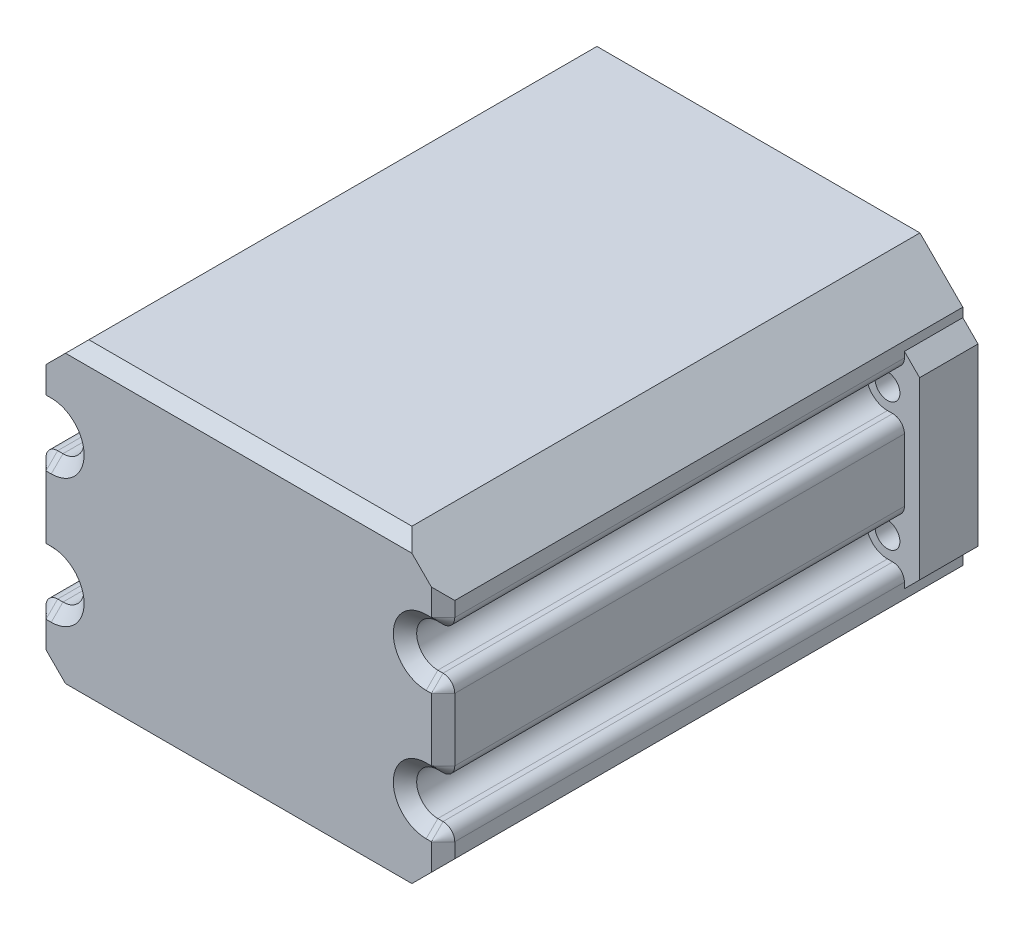
SolidWorks part; units mm, degrees
note: The reader was unsure of these and kept them because the rebuilt part matched: shared geometry of "Sketch1<3>".
ref_plane "Front Plane" through (0, 0, 0) normal (0, 0, 1) x (1, 0, 0)
ref_plane "Top Plane" through (0, 0, 0) normal (0, 1, 0) x (1, 0, 0)
ref_plane "Right Plane" through (0, 0, 0) normal (1, 0, 0) x (0, 0, -1)
sketch "Sketch1" plane through (0, 0, 0) normal (0, 0, 1) x (1, 0, 0)
  line L0 (27.6569, 53) -> (27.6569, 0) construction
  line L2 (-3.3431, 9.6017) -> (-3.3431, 9)
  line L4 (-4.4431, 41.125) -> (-7.3431, 41.125)
  line L5 (-4.4431, 33.875) -> (-7.3431, 33.875)
  line L6 (-4.4431, 11.875) -> (-7.3431, 11.875)
  line L7 (-4.4431, 19.125) -> (-7.3431, 19.125)
  line L8 (-7.3431, 41.5) -> (-9.9431, 41.5)
  line L13 (-9.9431, 41.5) -> (-9.9431, 11.5)
  line L17 (55.3137, 53) -> (0, 53)
  line L18 (0, 53) -> (-7.3431, 45.6569)
  line L19 (-7.3431, 45.6569) -> (-7.3431, 41.125)
  line L20 (-7.3431, 7.3431) -> (0, 0)
  line L21 (0, 0) -> (55.3137, 0)
  line L28 (-7.3431, 11.875) -> (-7.3431, 7.3431)
  line L29 (-7.3431, 33.875) -> (-7.3431, 19.125)
  line L30 (-7.3431, 33.875) -> (-7.3431, 19.125)
  line L33 (27.6569, 49) -> (1.6569, 49)
  line L37 (1.6569, 4) -> (27.6569, 4)
  line L38 (-3.3431, 9) -> (1.6569, 4)
  line L44 (1.5569, 37.5) -> (1.5569, 15.5)
  line L46 (1.6569, 49) -> (-3.3431, 44)
  line L47 (-3.3431, 44) -> (-3.3431, 43.3983)
  line L50 (-9.9431, 11.5) -> (-7.3431, 11.5)
  line L57 (65.2569, 11.5) -> (62.6569, 11.5)
  line L58 (58.6569, 44) -> (58.6569, 43.3983)
  line L59 (53.6569, 49) -> (58.6569, 44)
  line L60 (53.7569, 37.5) -> (53.7569, 15.5)
  line L61 (58.6569, 9) -> (53.6569, 4)
  line L62 (53.6569, 4) -> (27.6569, 4)
  line L63 (27.6569, 49) -> (53.6569, 49)
  line L64 (62.6569, 33.875) -> (62.6569, 19.125)
  line L66 (62.6569, 33.875) -> (62.6569, 19.125)
  line L67 (62.6569, 11.875) -> (62.6569, 7.3431)
  line L68 (62.6569, 7.3431) -> (55.3137, 0)
  line L70 (62.6569, 45.6569) -> (62.6569, 41.125)
  line L71 (55.3137, 53) -> (62.6569, 45.6569)
  line L72 (65.2569, 41.5) -> (65.2569, 11.5)
  line L73 (62.6569, 41.5) -> (65.2569, 41.5)
  line L74 (59.7569, 19.125) -> (62.6569, 19.125)
  line L75 (59.7569, 11.875) -> (62.6569, 11.875)
  line L76 (59.7569, 33.875) -> (62.6569, 33.875)
  line L77 (59.7569, 41.125) -> (62.6569, 41.125)
  line L78 (58.6569, 9.6017) -> (58.6569, 9)
  line L79 (-9.9431, 41.5) -> (-9.9431, 11.5) construction
  line L80 (-9.9431, 41.5) -> (-7.3431, 44.1)
  line L81 (-9.9431, 11.5) -> (-7.3431, 8.9)
  line L82 (-7.3431, 8.9) -> (-7.3431, 11.5)
  line L83 (-7.3431, 44.1) -> (-7.3431, 41.5)
  line L84 (62.6569, 41.5) -> (65.2569, 41.5)
  line L85 (65.2569, 41.5) -> (62.6569, 44.1)
  line L86 (65.2569, 41.5) -> (62.6569, 44.1) construction
  line L87 (62.6569, 44.1) -> (62.6569, 41.5)
  line L88 (65.2569, 11.5) -> (62.6569, 8.9)
  line L89 (62.6569, 8.9) -> (65.2569, 11.5) construction
  line L90 (62.6569, 8.9) -> (62.6569, 11.5)
  arc A0 (-4.4431, 33.875) -> (-4.4431, 41.125) centre (-4.4431, 37.5) ccw
  circle A1 centre (-4.4431, 15.5) radius 2.125
  circle A4 centre (-4.4431, 37.5) radius 2.125
  arc A5 (-4.4431, 11.875) -> (-4.4431, 19.125) centre (-4.4431, 15.5) ccw
  arc A14 (58.6569, 9.6017) -> (53.7569, 15.5) centre (59.7569, 15.5) cw
  arc A26 (1.5569, 37.5) -> (-3.3431, 43.3983) centre (-4.4431, 37.5) ccw
  arc A27 (-3.3431, 9.6017) -> (1.5569, 15.5) centre (-4.4431, 15.5) ccw
  arc A28 (53.7569, 37.5) -> (58.6569, 43.3983) centre (59.7569, 37.5) cw
  arc A29 (59.7569, 11.875) -> (59.7569, 19.125) centre (59.7569, 15.5) cw
  circle A30 centre (59.7569, 37.5) radius 2.125
  circle A31 centre (59.7569, 15.5) radius 2.125
  arc A32 (59.7569, 33.875) -> (59.7569, 41.125) centre (59.7569, 37.5) cw
  point P43 (14.6569, 4)
  point P44 (14.6569, 49)
  point P63 (40.6569, 49)
  point P64 (40.6569, 4)
  point P75 (1.5569, 26.5)
  point P76 (27.6569, 26.5)
  dimension "D3" = 7.25
  dimension "D4" = 4.25
  dimension "D5" = 12
  dimension "D6" = 22
  dimension "D7" = 32.1
  dimension "D1" = 45
  dimension "D2" = 45
  dimension "D8" = 4
  dimension "D9" = 45
  dimension "D10" = 5
  dimension "D11" = 4
  dimension "D12" = 4
  dimension "D13" = 4
  dimension "D14" = 5
  dimension "D15" = 4
  dimension "D16" = 31
extrude "Boss-Extrude1" add sketch "Sketch1" along normal blind 85
extrude "Boss-Extrude2" add sketch "Sketch1<3>" along normal blind 10
sketch "Sketch1<3>" plane through (0, 0, 0) normal (0, 0, 1) x (1, 0, 0) same geometry as "Sketch1"
fillet "Fillet1" radius 2 8 edges at (-7.3431, 41.125, 47.5) (-7.3431, 19.125, 47.5) (-7.3431, 11.875, 47.5) (-7.3431, 33.875, 47.5) (62.6569, 41.125, 47.5) (62.6569, 33.875, 47.5) (62.6569, 19.125, 47.5) (62.6569, 11.875, 47.5)
sketch "Sketch2" plane through (0, 0, 85) normal (0, 0, 1) x (1, 0, 0)
  line L21 (-7.3431, 31.875) -> (-7.3431, 21.125)
  line L28 (-7.3431, 9.875) -> (-7.3431, 7.3431)
  line L37 (55.3137, 0) -> (62.6569, 7.3431)
  line L43 (55.3137, 53) -> (0, 53)
  line L44 (0, 53) -> (-7.3431, 45.6569)
  line L45 (-7.3431, 45.6569) -> (-7.3431, 43.125)
  line L46 (-5.3431, 41.125) -> (-4.4431, 41.125)
  line L47 (-4.4431, 33.875) -> (-5.3431, 33.875)
  line L49 (-5.3431, 19.125) -> (-4.4431, 19.125)
  line L50 (-4.4431, 11.875) -> (-5.3431, 11.875)
  line L52 (-7.3431, 7.3431) -> (0, 0)
  line L53 (0, 0) -> (55.3137, 0)
  line L72 (62.6569, 7.3431) -> (62.6569, 9.875)
  line L82 (60.6569, 11.875) -> (59.7569, 11.875)
  line L86 (59.7569, 19.125) -> (60.6569, 19.125)
  line L90 (62.6569, 21.125) -> (62.6569, 31.875)
  line L92 (60.6569, 33.875) -> (59.7569, 33.875)
  line L94 (59.7569, 41.125) -> (60.6569, 41.125)
  line L96 (62.6569, 43.125) -> (62.6569, 45.6569)
  line L98 (62.6569, 45.6569) -> (55.3137, 53)
  arc A12 (59.7569, 19.125) -> (59.7569, 11.875) centre (59.7569, 15.5) ccw
  arc A15 (59.7569, 41.125) -> (59.7569, 33.875) centre (59.7569, 37.5) ccw
  arc A18 (-7.3431, 43.125) -> (-5.3431, 41.125) centre (-5.3431, 43.125) ccw
  arc A23 (-5.3431, 33.875) -> (-7.3431, 31.875) centre (-5.3431, 31.875) ccw
  arc A31 (-7.3431, 21.125) -> (-5.3431, 19.125) centre (-5.3431, 21.125) ccw
  arc A35 (-5.3431, 11.875) -> (-7.3431, 9.875) centre (-5.3431, 9.875) ccw
  arc A46 (-4.4431, 33.875) -> (-4.4431, 41.125) centre (-4.4431, 37.5) ccw
  arc A49 (-4.4431, 11.875) -> (-4.4431, 19.125) centre (-4.4431, 15.5) ccw
  arc A62 (60.6569, 41.125) -> (62.6569, 43.125) centre (60.6569, 43.125) ccw
  arc A64 (62.6569, 9.875) -> (60.6569, 11.875) centre (60.6569, 9.875) ccw
  arc A66 (60.6569, 19.125) -> (62.6569, 21.125) centre (60.6569, 21.125) ccw
  arc A68 (62.6569, 31.875) -> (60.6569, 33.875) centre (60.6569, 31.875) ccw
extrude "Boss-Extrude3" add sketch "Sketch2" along normal blind 4
chamfer "Chamfer1" distance 2 angle 45 28 edges at (27.6569, 0, 89) (27.6569, 53, 89) (-4.8931, 11.875, 89) (-0.8181, 15.5, 89) (-4.8931, 19.125, 89) (-7.3431, 44.3909, 89) (-7.3431, 26.5, 89) (-7.3431, 8.6091, 89) (-6.7574, 41.7108, 89) (-4.8931, 41.125, 89) (-4.8931, 33.875, 89) (-0.8181, 37.5, 89) (-6.7574, 11.2892, 89) (-6.7574, 19.7108, 89) (-6.7574, 33.2892, 89) (62.6569, 8.6091, 89) (62.6569, 44.3909, 89) (62.0711, 11.2892, 89) (62.0711, 41.7108, 89) (60.2069, 11.875, 89) (60.2069, 41.125, 89) (56.1319, 15.5, 89) (56.1319, 37.5, 89) (60.2069, 19.125, 89) (60.2069, 33.875, 89) (62.0711, 19.7108, 89) (62.0711, 33.2892, 89) (62.6569, 26.5, 89)
